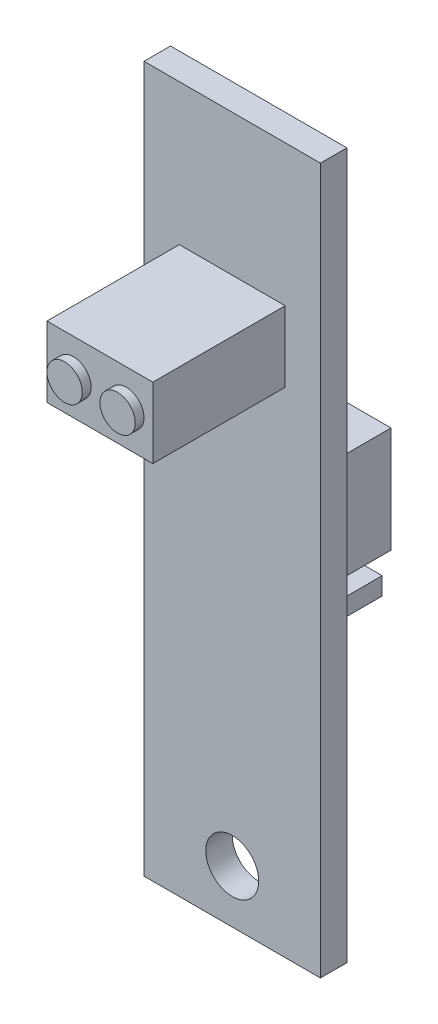
SolidWorks part; units mm, degrees
ref_plane "前基準面" through (0, 0, 0) normal (0, 0, 1) x (1, 0, 0)
ref_plane "上基準面" through (0, 0, 0) normal (0, 1, 0) x (1, 0, 0)
ref_plane "右基準面" through (0, 0, 0) normal (1, 0, 0) x (0, 0, -1)
sketch "草圖2" plane through (0, 0, 0) normal (0, 0, 1) x (1, 0, 0)
  line L1 (0, 0) -> (10, 0)
  line L2 (0, 0) -> (0, 40)
  line L3 (0, 40) -> (10, 40)
  line L4 (10, 0) -> (10, 40)
  circle A0 centre (5, 3) radius 1.5
  dimension "D4" = 3
  dimension "D1" = 40
  dimension "D2" = 10
  dimension "D3" = 3
extrude "填料-伸長1" add sketch "草圖2" along normal blind 1.5
sketch "草圖3" plane through (0, 0, 1.5) normal (0, 0, 1) x (1, 0, 0)
  line L0 (10, 0) -> (10, 40) construction
  line L1 (0, 40) -> (10, 40)
  line L2 (0, 40) -> (0, 20)
  line L3 (0, 20) -> (10, 20)
  line L4 (10, 40) -> (10, 20)
  line L5 (2, 14) -> (8, 14)
  line L6 (0, 40) -> (10, 40)
  line L7 (0, 40) -> (0, 30)
  line L8 (0, 30) -> (10, 30)
  line L9 (10, 40) -> (10, 30)
  line L10 (0, 40) -> (10, 40)
  line L11 (0, 40) -> (0, 15)
  line L12 (0, 15) -> (10, 15)
  line L13 (10, 40) -> (10, 15)
  line L14 (8, 23) -> (2, 23)
  line L15 (8, 23) -> (8, 17)
  line L16 (8, 17) -> (2, 17)
  line L17 (2, 23) -> (2, 17)
  line L18 (2, 15) -> (8, 15)
  line L19 (2, 14) -> (2, 16)
  line L20 (2, 16) -> (8, 16)
  line L21 (8, 14) -> (8, 16)
  line L22 (2, 32) -> (8, 32)
  line L23 (2, 30) -> (8, 30)
  line L24 (2, 32) -> (2, 28)
  line L25 (2, 28) -> (8, 28)
  line L26 (8, 32) -> (8, 28)
  circle A0 centre (5, 20) radius 3
  dimension "D4" = 1
  dimension "D1" = 20
  dimension "D2" = 10
  dimension "D3" = 25
  dimension "D5" = 2
extrude "填料-伸長2" add sketch "草圖3" along normal blind 8 contours L22 L26 L25 L24
extrude "填料-伸長3" add sketch "草圖3<3>" against normal blind 6 contours L14 L17 L16 L15
sketch "草圖3<3>" plane through (0, 0, 1.5) normal (0, 0, 1) x (1, 0, 0) same geometry as "草圖3"
extrude "填料-伸長4" add sketch "草圖3<4>" against normal blind 2 contours L21 L20 L19 L5
sketch "草圖3<4>" plane through (0, 0, 1.5) normal (0, 0, 1) x (1, 0, 0) same geometry as "草圖3"
sketch "草圖4" plane through (0, 0, -0.5) normal (0, 0, -1) x (-1, 0, 0)
  line L0 (-2, 14) -> (-8, 14) construction
  line L1 (-8, 16) -> (-6, 16)
  line L2 (-8, 16) -> (-8, 14)
  line L3 (-8, 14) -> (-6, 14)
  line L4 (-6, 16) -> (-6, 14)
  line L5 (-4, 16) -> (-4, 14)
  line L6 (-6, 16) -> (-4, 16)
  line L7 (-6, 16) -> (-6, 14)
  line L8 (-6, 14) -> (-4, 14)
  line L9 (-2, 16) -> (-2, 14)
  line L10 (-4, 16) -> (-2, 16)
  line L11 (-4, 16) -> (-4, 14)
  line L12 (-4, 14) -> (-2, 14)
  line L13 (-4.5, 15.5) -> (-5.5, 15.5)
  line L14 (-5.5, 15.5) -> (-5.5, 14.5)
  line L15 (-4.5, 14.5) -> (-5.5, 14.5)
  line L16 (-6.5, 15.5) -> (-7.5, 15.5)
  line L17 (-6.5, 15.5) -> (-6.5, 14.5)
  line L18 (-6.5, 14.5) -> (-7.5, 14.5)
  line L19 (-7.5, 15.5) -> (-7.5, 14.5)
  line L20 (-4.5, 15.5) -> (-4.5, 14.5)
  line L21 (-2.5, 15.5) -> (-3.5, 15.5)
  line L22 (-3.5, 15.5) -> (-3.5, 14.5)
  line L23 (-2.5, 14.5) -> (-3.5, 14.5)
  line L24 (-2.5, 15.5) -> (-2.5, 14.5)
  dimension "D3" = 3
  dimension "D1" = 2
  dimension "D2" = 3
extrude "填料-伸長5" add sketch "草圖4" along normal blind 4 contours L16 L19 L18 L17 | L20 L13 L14 L15 | L24 L21 L22 L23 region at (5, 15, -0.5) region at (7, 15, -0.5) region at (3, 15, -0.5)
sketch "草圖5" plane through (0, 0, 9.5) normal (0, 0, 1) x (1, 0, 0)
  line L1 (8, 32) -> (2, 32)
  line L2 (8, 32) -> (8, 28)
  line L3 (8, 28) -> (2, 28)
  line L4 (2, 32) -> (2, 28)
  circle A0 centre (3.5, 30) radius 1
  circle A1 centre (6.5, 30) radius 1
  dimension "D3" = 2
  dimension "D4" = 2
  dimension "D1" = 1.5
  dimension "D2" = 1.5
extrude "除料-伸長1" cut sketch "草圖5" against normal blind 0.5
